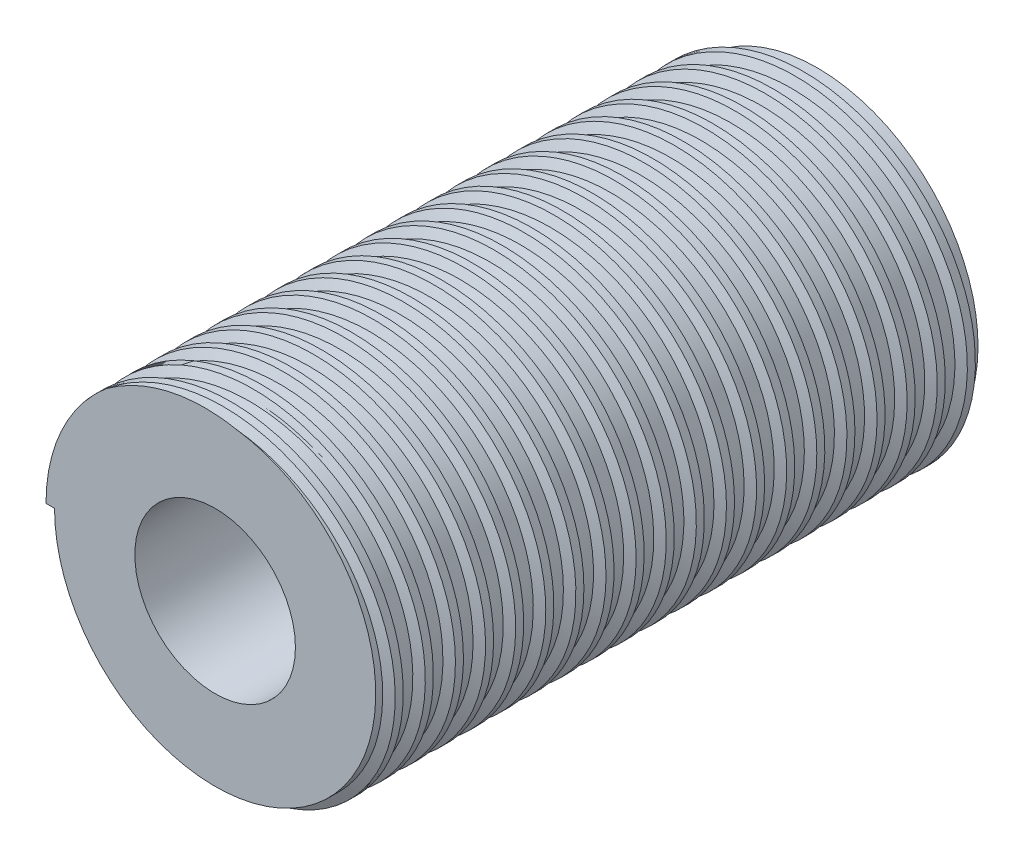
SolidWorks part; units mm, degrees
ref_plane "Front Plane" through (0, 0, 0) normal (0, 0, 1) x (1, 0, 0)
ref_plane "Top Plane" through (0, 0, 0) normal (0, 1, 0) x (1, 0, 0)
ref_plane "Right Plane" through (0, 0, 0) normal (1, 0, 0) x (0, 0, -1)
sketch "Sketch1" plane through (0, 0, 0) normal (0, 0, 1) x (1, 0, 0)
  circle A0 centre (0, 0) radius 8
  circle A1 centre (0, 0) radius 6
  dimension "D1" = 16
  dimension "D2" = 12
extrude "Boss-Extrude1" add sketch "Sketch1" along normal blind 30
sketch "Sketch2" plane through (0, 0, 0) normal (0, 0, -1) x (-1, 0, 0)
  circle A0 centre (0, 0) radius 8
curve "Helix/Spiral1" pitch 1.5 height 30 radius 8 centre (0, 0, 0) axis (0, 0, 1) start towards (-1, 0, 0)
sketch "Sketch3" plane through (0, 0, 0) normal (0, 1, 0) x (1, 0, 0)
  line L0 (7.9955, -2.258) -> (8.4244, -2.258) construction
  line L1 (7.9955, -1.858) -> (7.9955, -2.658)
  line L2 (7.9955, -2.658) -> (8.4244, -2.458)
  line L3 (8.4244, -2.458) -> (8.4244, -2.058)
  line L4 (7.9955, -1.858) -> (8.4244, -2.058)
  spline S0 degree 3 poles (-8, 0) (-8, -0.031) (-7.5835, -0.0938) (-5.8041, -0.1875) (-3.1412, -0.2813) (0, -0.375) (3.1412, -0.4688) (5.8041, -0.5625) (7.5835, -0.6563) (8.2083, -0.75) (7.5835, -0.8438) (5.8041, -0.9375) (2.2535, -1.0625) (-2.2535, -1.1875) (-5.8041, -1.3125) (-7.5835, -1.4063) (-8.2083, -1.5) (-7.5835, -1.5938) (-5.8041, -1.6875) (-2.2535, -1.8125) (2.2535, -1.9375) (5.8041, -2.0625) (7.5835, -2.1563) (8.2083, -2.25) (7.5835, -2.3438) (5.8041, -2.4375) (2.2535, -2.5625) (-2.2535, -2.6875) (-5.8041, -2.8125) (-7.5835, -2.9063) (-8.2083, -3) (-7.5835, -3.0938) (-5.8041, -3.1875) (-2.2535, -3.3125) (2.2535, -3.4375) (5.8041, -3.5625) (7.5835, -3.6563) (8.2083, -3.75) (7.5835, -3.8438) (5.8041, -3.9375) (2.2535, -4.0625) (-2.2535, -4.1875) (-5.8041, -4.3125) (-7.5835, -4.4063) (-8.2083, -4.5) (-7.5835, -4.5938) (-5.8041, -4.6875) (-2.2535, -4.8125) (2.2535, -4.9375) (5.8041, -5.0625) (7.5835, -5.1563) (8.2083, -5.25) (7.5835, -5.3438) (5.8041, -5.4375) (2.2535, -5.5625) (-2.2535, -5.6875) (-5.8041, -5.8125) (-7.5835, -5.9063) (-8.2083, -6) (-7.5835, -6.0938) (-5.8041, -6.1875) (-2.2535, -6.3125) (2.2535, -6.4375) (5.8041, -6.5625) (7.5835, -6.6563) (8.2083, -6.75) (7.5835, -6.8438) (5.8041, -6.9375) (2.2535, -7.0625) (-2.2535, -7.1875) (-5.8041, -7.3125) (-7.5835, -7.4063) (-8.2083, -7.5) (-7.5835, -7.5938) (-5.8041, -7.6875) (-2.2535, -7.8125) (2.2535, -7.9375) (5.8041, -8.0625) (7.5835, -8.1563) (8.2083, -8.25) (7.5835, -8.3438) (5.8041, -8.4375) (2.2535, -8.5625) (-2.2535, -8.6875) (-5.8041, -8.8125) (-7.5835, -8.9063) (-8.2083, -9) (-7.5835, -9.0938) (-5.8041, -9.1875) (-2.2535, -9.3125) (2.2535, -9.4375) (5.8041, -9.5625) (7.5835, -9.6563) (8.2083, -9.75) (7.5835, -9.8438) (5.8041, -9.9375) (2.2535, -10.0625) (-2.2535, -10.1875) (-5.8041, -10.3125) (-7.5835, -10.4063) (-8.2083, -10.5) (-7.5835, -10.5938) (-5.8041, -10.6875) (-2.2535, -10.8125) (2.2535, -10.9375) (5.8041, -11.0625) (7.5835, -11.1563) (8.2083, -11.25) (7.5835, -11.3438) (5.8041, -11.4375) (2.2535, -11.5625) (-2.2535, -11.6875) (-5.8041, -11.8125) (-7.5835, -11.9063) (-8.2083, -12) (-7.5835, -12.0938) (-5.8041, -12.1875) (-2.2535, -12.3125) (2.2535, -12.4375) (5.8041, -12.5625) (7.5835, -12.6563) (8.2083, -12.75) (7.5835, -12.8438) (5.8041, -12.9375) (2.2535, -13.0625) (-2.2535, -13.1875) (-5.8041, -13.3125) (-7.5835, -13.4063) (-8.2083, -13.5) (-7.5835, -13.5938) (-5.8041, -13.6875) (-2.2535, -13.8125) (2.2535, -13.9375) (5.8041, -14.0625) (7.5835, -14.1563) (8.2083, -14.25) (7.5835, -14.3438) (5.8041, -14.4375) (2.2535, -14.5625) (-2.2535, -14.6875) (-5.8041, -14.8125) (-7.5835, -14.9063) (-8.2083, -15) (-7.5835, -15.0938) (-5.8041, -15.1875) (-2.2535, -15.3125) (2.2535, -15.4375) (5.8041, -15.5625) (7.5835, -15.6563) (8.2083, -15.75) (7.5835, -15.8438) (5.8041, -15.9375) (2.2535, -16.0625) (-2.2535, -16.1875) (-5.8041, -16.3125) (-7.5835, -16.4063) (-8.2083, -16.5) (-7.5835, -16.5938) (-5.8041, -16.6875) (-2.2535, -16.8125) (2.2535, -16.9375) (5.8041, -17.0625) (7.5835, -17.1563) (8.2083, -17.25) (7.5835, -17.3438) (5.8041, -17.4375) (2.2535, -17.5625) (-2.2535, -17.6875) (-5.8041, -17.8125) (-7.5835, -17.9063) (-8.2083, -18) (-7.5835, -18.0938) (-5.8041, -18.1875) (-2.2535, -18.3125) (2.2535, -18.4375) (5.8041, -18.5625) (7.5835, -18.6563) (8.2083, -18.75) (7.5835, -18.8438) (5.8041, -18.9375) (2.2535, -19.0625) (-2.2535, -19.1875) (-5.8041, -19.3125) (-7.5835, -19.4063) (-8.2083, -19.5) (-7.5835, -19.5938) (-5.8041, -19.6875) (-2.2535, -19.8125) (2.2535, -19.9375) (5.8041, -20.0625) (7.5835, -20.1563) (8.2083, -20.25) (7.5835, -20.3438) (5.8041, -20.4375) (2.2535, -20.5625) (-2.2535, -20.6875) (-5.8041, -20.8125) (-7.5835, -20.9063) (-8.2083, -21) (-7.5835, -21.0938) (-5.8041, -21.1875) (-2.2535, -21.3125) (2.2535, -21.4375) (5.8041, -21.5625) (7.5835, -21.6563) (8.2083, -21.75) (7.5835, -21.8438) (5.8041, -21.9375) (2.2535, -22.0625) (-2.2535, -22.1875) (-5.8041, -22.3125) (-7.5835, -22.4063) (-8.2083, -22.5) (-7.5835, -22.5938) (-5.8041, -22.6875) (-2.2535, -22.8125) (2.2535, -22.9375) (5.8041, -23.0625) (7.5835, -23.1563) (8.2083, -23.25) (7.5835, -23.3438) (5.8041, -23.4375) (2.2535, -23.5625) (-2.2535, -23.6875) (-5.8041, -23.8125) (-7.5835, -23.9063) (-8.2083, -24) (-7.5835, -24.0938) (-5.8041, -24.1875) (-2.2535, -24.3125) (2.2535, -24.4375) (5.8041, -24.5625) (7.5835, -24.6563) (8.2083, -24.75) (7.5835, -24.8438) (5.8041, -24.9375) (2.2535, -25.0625) (-2.2535, -25.1875) (-5.8041, -25.3125) (-7.5835, -25.4063) (-8.2083, -25.5) (-7.5835, -25.5938) (-5.8041, -25.6875) (-2.2535, -25.8125) (2.2535, -25.9375) (5.8041, -26.0625) (7.5835, -26.1563) (8.2083, -26.25) (7.5835, -26.3438) (5.8041, -26.4375) (2.2535, -26.5625) (-2.2535, -26.6875) (-5.8041, -26.8125) (-7.5835, -26.9063) (-8.2083, -27) (-7.5835, -27.0938) (-5.8041, -27.1875) (-2.2535, -27.3125) (2.2535, -27.4375) (5.8041, -27.5625) (7.5835, -27.6563) (8.2083, -27.75) (7.5835, -27.8438) (5.8041, -27.9375) (2.2535, -28.0625) (-2.2535, -28.1875) (-5.8041, -28.3125) (-7.5835, -28.4062) (-8.2083, -28.5) (-7.5835, -28.5937) (-5.8041, -28.6875) (-2.2535, -28.8125) (2.2535, -28.9375) (5.8041, -29.0625) (7.5835, -29.1562) (8.2083, -29.25) (7.5835, -29.3437) (5.8041, -29.4375) (3.1412, -29.5312) (0, -29.625) (-3.1412, -29.7187) (-5.8041, -29.8125) (-7.5835, -29.9062) (-8, -29.969) (-8, -30) knots 0 0 0 0 0.003125 0.00625 0.009375 0.0125 0.015625 0.01875 0.021875 0.025 0.028125 0.03125 0.034375 0.040625 0.04375 0.046875 0.05 0.053125 0.05625 0.059375 0.065625 0.06875 0.071875 0.075 0.078125 0.08125 0.084375 0.090625 0.09375 0.096875 0.1 0.103125 0.10625 0.109375 0.115625 0.11875 0.121875 0.125 0.128125 0.13125 0.134375 0.140625 0.14375 0.146875 0.15 0.153125 0.15625 0.159375 0.165625 0.16875 0.171875 0.175 0.178125 0.18125 0.184375 0.190625 0.19375 0.196875 0.2 0.203125 0.20625 0.209375 0.215625 0.21875 0.221875 0.225 0.228125 0.23125 0.234375 0.240625 0.24375 0.246875 0.25 0.253125 0.25625 0.259375 0.265625 0.26875 0.271875 0.275 0.278125 0.28125 0.284375 0.290625 0.29375 0.296875 0.3 0.303125 0.30625 0.309375 0.315625 0.31875 0.321875 0.325 0.328125 0.33125 0.334375 0.340625 0.34375 0.346875 0.35 0.353125 0.35625 0.359375 0.365625 0.36875 0.371875 0.375 0.378125 0.38125 0.384375 0.390625 0.39375 0.396875 0.4 0.403125 0.40625 0.409375 0.415625 0.41875 0.421875 0.425 0.428125 0.43125 0.434375 0.440625 0.44375 0.446875 0.45 0.453125 0.45625 0.459375 0.465625 0.46875 0.471875 0.475 0.478125 0.48125 0.484375 0.490625 0.49375 0.496875 0.5 0.503125 0.50625 0.509375 0.515625 0.51875 0.521875 0.525 0.528125 0.53125 0.534375 0.540625 0.54375 0.546875 0.55 0.553125 0.55625 0.559375 0.565625 0.56875 0.571875 0.575 0.578125 0.58125 0.584375 0.590625 0.59375 0.596875 0.6 0.603125 0.60625 0.609375 0.615625 0.61875 0.621875 0.625 0.628125 0.63125 0.634375 0.640625 0.64375 0.646875 0.65 0.653125 0.65625 0.659375 0.665625 0.66875 0.671875 0.675 0.678125 0.68125 0.684375 0.690625 0.69375 0.696875 0.7 0.703125 0.70625 0.709375 0.715625 0.71875 0.721875 0.725 0.728125 0.73125 0.734375 0.740625 0.74375 0.746875 0.75 0.753125 0.75625 0.759375 0.765625 0.76875 0.771875 0.775 0.778125 0.78125 0.784375 0.790625 0.79375 0.796875 0.8 0.803125 0.80625 0.809375 0.815625 0.81875 0.821875 0.825 0.828125 0.83125 0.834375 0.840625 0.84375 0.846875 0.85 0.853125 0.85625 0.859375 0.865625 0.86875 0.871875 0.875 0.878125 0.88125 0.884375 0.890625 0.89375 0.896875 0.9 0.903125 0.90625 0.909375 0.915625 0.91875 0.921875 0.925 0.928125 0.93125 0.934375 0.940625 0.94375 0.946875 0.95 0.953125 0.95625 0.959375 0.965625 0.96875 0.971875 0.975 0.978125 0.98125 0.984375 0.9875 0.990625 0.99375 0.996875 1 1 1 1 construction
  dimension "D1" = 0.2
  dimension "D2" = 0.4
  dimension "D3" = 65
sweep "Sweep1" add profiles "Sketch3" path "Helix/Spiral1"
sketch "Sketch4" plane through (0, 0, 30) normal (0, 0, 1) x (1, 0, 0)
  circle A0 centre (0, 0) radius 9.2621
extrude "Cut-Extrude1" cut sketch "Sketch4" along normal blind 25
sketch "Sketch5" plane through (0, 0, 0) normal (0, 0, -1) x (-1, 0, 0)
  circle A0 centre (0, 0) radius 14.4642
extrude "Cut-Extrude2" cut sketch "Sketch5" along normal blind 25
sketch "Sketch6" plane through (0, 0, 30) normal (0, 0, 1) x (1, 0, 0)
  circle A0 centre (0, 0) radius 6
  circle A1 centre (0, 0) radius 4
  dimension "D1" = 8
extrude "Boss-Extrude2" add sketch "Sketch6" against normal blind 20
